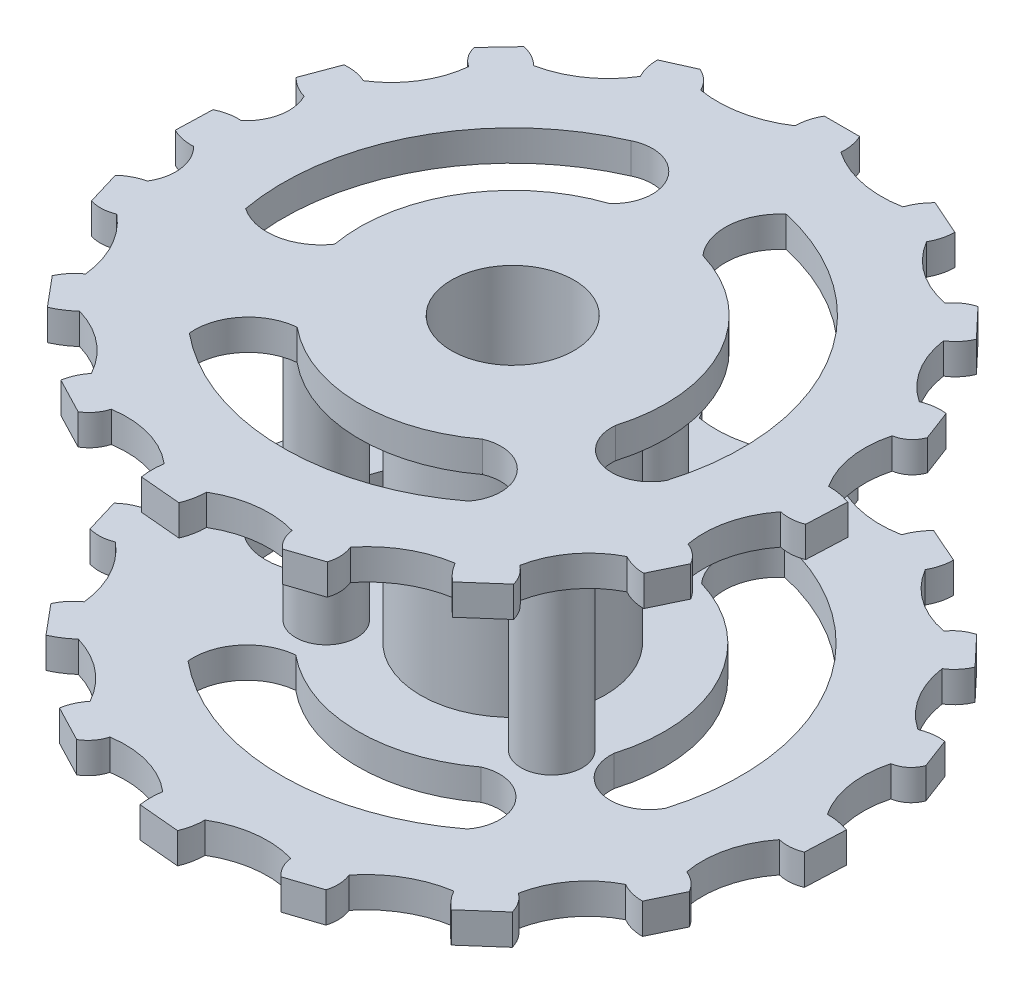
SolidWorks part; units mm, degrees
note: The reader was unsure of these and kept them because the rebuilt part matched: shared geometry of "Croquis5<6>".
ref_plane "Alzado" through (0, 0, 0) normal (0, 0, 1) x (1, 0, 0)
ref_plane "Planta" through (0, 0, 0) normal (0, 1, 0) x (1, 0, 0)
ref_plane "Vista lateral" through (0, 0, 0) normal (1, 0, 0) x (0, 0, -1)
sketch "Croquis1" plane through (0, 0, 0) normal (0, 1, 0) x (1, 0, 0)
  line L1 (7.418, 20.1666) -> (9.737, 19.1413)
  line L2 (14.6937, 15.6953) -> (16.489, 13.7972)
  line L3 (19.7018, 8.6076) -> (20.4553, 6.6204)
  line L4 (21.3822, -2.2476) -> (21.4965, 0.3858)
  line L5 (13.1137, -17.0376) -> (15.2348, -15.1707)
  line L6 (18.8688, -10.3062) -> (19.8608, -8.234)
  line L7 (5.6933, -20.7325) -> (7.8899, -20)
  line L8 (-2.9903, -21.2583) -> (-0.3023, -21.4979)
  line L9 (-8.7432, -19.6419) -> (-11.0959, -18.4155)
  line L10 (-15.6524, -14.7395) -> (-17.2801, -12.7925)
  line L11 (-20.2277, -7.2862) -> (-20.8986, -5.0496)
  line L12 (-21.4932, -0.5408) -> (-21.4205, 1.8468)
  line L13 (-20.53, 6.3852) -> (-19.6776, 8.6626)
  line L17 (1.2087, 21.4476) -> (-1.0939, 21.4476)
  line L24 (0, 8.75) -> (0, 7.75)
  line L27 (7.3634, -4.7268) -> (7.3634, -3.7268)
  line L28 (-7.3634, -4.7268) -> (-7.3634, -3.7268)
  line L33 (0, 20) -> (0, 19.3)
  line L34 (-9.7228, 19.176) -> (-7.8018, 20.0345)
  line L65 (-16.4043, 13.8978) -> (-14.8257, 15.5708)
  line L66 (-9.7228, 19.176) -> (-7.8018, 20.0345)
  arc A19 (-9.3513, 17.6792) -> (-9.7228, 19.176) centre (-6.5215, 19.176) cw
  arc A20 (-6.6037, 18.8783) -> (-7.8018, 20.0345) centre (-8.7432, 17.86) ccw
  arc A21 (19.8608, -2.3556) -> (21.3822, -2.2476) centre (20.4553, 0.0398) ccw
  arc A22 (19.9895, 0.6481) -> (21.4965, 0.3858) centre (19.9895, -3.8128) cw
  arc A23 (18.6573, -7.2045) -> (19.8608, -8.234) centre (17.7999, -9.4249) cw
  arc A24 (17.3725, -9.9095) -> (18.8688, -10.3062) centre (18.8688, -7.2862) ccw
  arc A25 (14.3713, -13.9092) -> (15.2348, -15.1707) centre (12.9424, -15.8135) cw
  arc A26 (12.1344, -15.8983) -> (13.1137, -17.0376) centre (15.6955, -13.8279) ccw
  arc A27 (7.8127, -18.4109) -> (7.8899, -20) centre (5.6933, -19.3103) cw
  arc A28 (4.9645, -19.374) -> (5.6933, -20.7325) centre (7.0961, -19.1053) ccw
  arc A29 (-2.9903, -19.7752) -> (-2.9903, -21.2583) centre (1.9139, -20.5168) ccw
  arc A30 (0, -20) -> (-0.3023, -21.4979) centre (-3.8625, -20) cw
  arc A31 (-7.8018, -18.4155) -> (-8.7432, -19.6419) centre (-9.8111, -17.8477) cw
  arc A32 (-10.4747, -17.0376) -> (-11.0959, -18.4155) centre (-8.1197, -18.9284) ccw
  arc A33 (-19.5247, -4.3341) -> (-20.8986, -5.0496) centre (-18.876, -7.2565) ccw
  arc A34 (-16.2897, -11.6037) -> (-17.2801, -12.7925) centre (-14.5249, -14.0811) ccw
  arc A35 (-14.3713, -13.9092) -> (-15.6524, -14.7395) centre (-17.6438, -10.2637) cw
  arc A36 (-18.6573, -7.2045) -> (-20.2277, -7.2862) centre (-19.5568, -5.0514) cw
  arc A37 (-19.8842, 2.1493) -> (-21.4205, 1.8468) centre (-20.0938, -0.8387) ccw
  arc A38 (-19.8492, -0.8562) -> (-21.4932, -0.5408) centre (-20.128, 2.1334) cw
  arc A39 (-19.2052, 5.582) -> (-20.53, 6.3852) centre (-18.3711, 8.4519) cw
  arc A40 (-18.1526, 8.3955) -> (-19.6776, 8.6626) centre (-19.4177, 5.6601) ccw
  arc A41 (-15.5056, 12.6323) -> (-16.4043, 13.8978) centre (-14.4368, 14.3432) cw
  arc A42 (-13.4419, 14.8093) -> (-14.8257, 15.5708) centre (-15.4964, 12.7141) ccw
  arc A43 (-1.5, 19.9437) -> (-1.0939, 21.4476) centre (1.488, 19.9437) cw
  arc A44 (1.488, 19.9437) -> (1.2087, 21.4476) centre (-1.5, 20.1666) ccw
  arc A45 (6.6037, 18.8783) -> (7.418, 20.1666) centre (9.7974, 17.7612) cw
  arc A47 (9.3513, 17.6792) -> (9.737, 19.1413) centre (6.773, 19.1413) ccw
  circle A48 centre (0, 0) radius 10
  arc A49 (1.488, 19.9437) -> (6.6037, 18.8783) centre (5.323, 25.5435) ccw
  arc A50 (9.3513, 17.6792) -> (13.4419, 14.8093) centre (14.5336, 20.7155) ccw
  arc A51 (15.5056, 12.6323) -> (18.1526, 8.3955) centre (21.6077, 13.4993) ccw
  arc A52 (19.2052, 5.582) -> (19.9895, 0.6481) centre (25.1101, 3.9913) ccw
  arc A53 (18.6573, -7.2045) -> (19.8608, -2.3556) centre (24.568, -6.0977) cw
  arc A54 (17.3725, -9.9095) -> (14.3713, -13.9092) centre (19.9576, -14.975) ccw
  arc A55 (12.1344, -15.8983) -> (7.8127, -18.4109) centre (13.1894, -22.686) ccw
  circle A56 centre (0, 0) radius 15
  arc A57 (0, -20) -> (4.9645, -19.374) centre (3.2011, -25.3884) cw
  arc A58 (-7.8018, -18.4155) -> (-2.9903, -19.7752) centre (-6.8649, -24.2932) cw
  arc A59 (-14.3713, -13.9092) -> (-10.4747, -17.0376) centre (-16.1823, -20.1557) cw
  arc A60 (-18.6573, -7.2045) -> (-16.2897, -11.6037) centre (-22.8771, -12.3123) cw
  arc A61 (-19.9895, -0.8568) -> (-19.5247, -4.3341) centre (-21.9152, -2.8839) cw
  arc A62 (-19.8842, 2.1493) -> (-19.2052, 5.582) centre (-21.712, 4.2943) ccw
  arc A63 (-18.1526, 8.3955) -> (-15.5056, 12.6323) centre (-21.1232, 13.1966) ccw
  arc A64 (-13.4419, 14.8093) -> (-9.3513, 17.6792) centre (-14.6867, 20.9337) ccw
  arc A65 (-6.6037, 18.8783) -> (-1.5, 19.9437) centre (-5.4022, 25.8803) ccw
  arc A66 (13.4419, 14.8093) -> (14.6937, 15.6953) centre (15.3083, 13.4999) cw
  arc A67 (15.5056, 12.6323) -> (16.489, 13.7972) centre (14.1868, 14.7433) ccw
  arc A68 (19.2052, 5.582) -> (20.4553, 6.6204) centre (18.9553, 7.1545) ccw
  arc A69 (18.1526, 8.3955) -> (19.7018, 8.6076) centre (19.3266, 5.5843) cw
  circle A71 centre (-7.3634, -4.7268) radius 1
  circle A72 centre (7.3634, -4.7268) radius 1
  circle A73 centre (0, 8.75) radius 1
  arc A74 (-6.0056, 13.7453) -> (-3.1657, 9.4857) centre (-4.878, 11.4206) cw
  arc A75 (3.2011, 14.6544) -> (2.8266, 9.5922) centre (5.545, 11.936) ccw
  arc A76 (14.3713, -4.2971) -> (9.5809, -2.8647) centre (12.1178, -3.1071) cw
  arc A77 (6.0162, -7.9878) -> (9.0619, -11.9534) centre (7.0185, -10.3703) cw
  arc A78 (-6.3717, -7.7072) -> (-9.5576, -11.5608) centre (-6.0378, -11.227) ccw
  arc A79 (-9.8388, -1.7882) -> (-14.7582, -2.6823) centre (-12.7456, 0.2245) cw
  circle A80 centre (0, 0) radius 1.5
  arc A81 (2.8266, 9.5922) -> (9.5809, -2.8647) centre (0, 0) cw
  arc A82 (6.0162, -7.9878) -> (-6.3717, -7.7072) centre (0, 0) cw
  arc A83 (-9.8388, -1.7882) -> (-3.1657, 9.4857) centre (0, 0) cw
  arc A84 (-6.0056, 13.7453) -> (-14.7582, -2.6823) centre (0, 0) ccw
  arc A85 (3.2011, 14.6544) -> (14.3713, -4.2971) centre (0, 0) cw
  arc A86 (9.0619, -11.9534) -> (-9.5576, -11.5608) centre (0, 0) cw
  dimension "D5" = 5
extrude "Saliente-Extruir1" add sketch "Croquis1" along normal blind 2
sketch "Croquis2" plane through (0, 2, 0) normal (0, 1, 0) x (1, 0, 0)
  line L0 (0, 0) -> (4, 0)
  line L1 (0, 0) -> (-6, 0)
  circle A2 centre (-7.3634, -4.7268) radius 2
  circle A3 centre (7.3634, -4.7268) radius 2
  circle A4 centre (0, 8.75) radius 2
  circle A5 centre (0, 0) radius 4
  dimension "D3" = 4
  dimension "D4" = 4
  dimension "D5" = 4
extrude "Saliente-Extruir2" add sketch "Croquis2" along normal blind 16.5
sketch "Croquis4" plane through (0, 18.5, 0) normal (0, 1, 0) x (1, 0, 0)
sketch "Croquis5" plane through (0, 18.5, 0) normal (0, 1, 0) x (1, 0, 0)
  line L0 (7.418, 20.2554) -> (9.737, 19.23)
  line L1 (14.6937, 15.7841) -> (16.489, 13.886)
  line L2 (19.7018, 8.6964) -> (20.4553, 6.7092)
  line L3 (21.3822, -2.1588) -> (21.4965, 0.4746)
  line L4 (13.1137, -16.9488) -> (15.2348, -15.0819)
  line L5 (18.8688, -10.2175) -> (19.8608, -8.1452)
  line L6 (5.6933, -20.6437) -> (7.8899, -19.9112)
  line L7 (-2.9903, -21.1695) -> (-0.3023, -21.4091)
  line L8 (-8.7432, -19.5531) -> (-11.0959, -18.3267)
  line L9 (-15.6524, -14.6507) -> (-17.2801, -12.7037)
  line L10 (-20.2277, -7.1974) -> (-20.8986, -4.9608)
  line L11 (-21.4932, -0.4521) -> (-21.4205, 1.9356)
  line L12 (-20.53, 6.4739) -> (-19.6776, 8.7514)
  line L13 (1.2087, 21.5364) -> (-1.0939, 21.5364)
  line L14 (0, 8.8388) -> (0, 7.8388)
  line L15 (7.3634, -4.638) -> (7.3634, -3.638)
  line L16 (-7.3634, -4.638) -> (-7.3634, -3.638)
  line L17 (0, 20.0888) -> (0, 19.3888)
  line L18 (-9.7228, 19.2648) -> (-7.8018, 20.1233)
  line L19 (-16.4043, 13.9866) -> (-14.8257, 15.6596)
  line L20 (-9.7228, 19.2648) -> (-7.8018, 20.1233)
  line L21 (0, 0.0888) -> (4, 0.0888)
  line L22 (0, 0.0888) -> (0, -5.9112)
  line L23 (0, 0) -> (3, 0)
  arc A0 (-9.3513, 17.768) -> (-9.7228, 19.2648) centre (-6.5215, 19.2648) cw
  arc A1 (-6.6037, 18.9671) -> (-7.8018, 20.1233) centre (-8.7432, 17.9488) ccw
  arc A2 (19.8608, -2.2668) -> (21.3822, -2.1588) centre (20.4553, 0.1285) ccw
  arc A3 (19.9895, 0.7369) -> (21.4965, 0.4746) centre (19.9895, -3.724) cw
  arc A4 (18.6573, -7.1157) -> (19.8608, -8.1452) centre (17.7999, -9.3361) cw
  arc A5 (17.3725, -9.8207) -> (18.8688, -10.2175) centre (18.8688, -7.1974) ccw
  arc A6 (14.3713, -13.8204) -> (15.2348, -15.0819) centre (12.9424, -15.7247) cw
  arc A7 (12.1344, -15.8095) -> (13.1137, -16.9488) centre (15.6955, -13.7392) ccw
  arc A8 (7.8127, -18.3221) -> (7.8899, -19.9112) centre (5.6933, -19.2215) cw
  arc A9 (4.9645, -19.2852) -> (5.6933, -20.6437) centre (7.0961, -19.0165) ccw
  arc A10 (-2.9903, -19.6864) -> (-2.9903, -21.1695) centre (1.9139, -20.428) ccw
  arc A11 (0, -19.9112) -> (-0.3023, -21.4091) centre (-3.8625, -19.9112) cw
  arc A12 (-7.8018, -18.3267) -> (-8.7432, -19.5531) centre (-9.8111, -17.7589) cw
  arc A13 (-10.4747, -16.9488) -> (-11.0959, -18.3267) centre (-8.1197, -18.8396) ccw
  arc A14 (-19.5247, -4.2453) -> (-20.8986, -4.9608) centre (-18.876, -7.1677) ccw
  arc A15 (-16.2897, -11.5149) -> (-17.2801, -12.7037) centre (-14.5249, -13.9923) ccw
  arc A16 (-14.3713, -13.8204) -> (-15.6524, -14.6507) centre (-17.6438, -10.1749) cw
  arc A17 (-18.6573, -7.1157) -> (-20.2277, -7.1974) centre (-19.5568, -4.9626) cw
  arc A18 (-19.8842, 2.2381) -> (-21.4205, 1.9356) centre (-20.0938, -0.7499) ccw
  arc A19 (-19.8492, -0.7674) -> (-21.4932, -0.4521) centre (-20.128, 2.2222) cw
  arc A20 (-19.2052, 5.6708) -> (-20.53, 6.4739) centre (-18.3711, 8.5407) cw
  arc A21 (-18.1526, 8.4843) -> (-19.6776, 8.7514) centre (-19.4177, 5.7489) ccw
  arc A22 (-15.5056, 12.7211) -> (-16.4043, 13.9866) centre (-14.4368, 14.432) cw
  arc A23 (-13.4419, 14.8981) -> (-14.8257, 15.6596) centre (-15.4964, 12.8028) ccw
  arc A24 (-1.5, 20.0325) -> (-1.0939, 21.5364) centre (1.488, 20.0325) cw
  arc A25 (1.488, 20.0325) -> (1.2087, 21.5364) centre (-1.5, 20.2554) ccw
  arc A26 (6.6037, 18.9671) -> (7.418, 20.2554) centre (9.7974, 17.8499) cw
  arc A27 (9.3513, 17.768) -> (9.737, 19.23) centre (6.773, 19.23) ccw
  circle A28 centre (0, 0.0888) radius 10
  arc A29 (1.488, 20.0325) -> (6.6037, 18.9671) centre (5.323, 25.6323) ccw
  arc A30 (9.3513, 17.768) -> (13.4419, 14.8981) centre (14.5336, 20.8043) ccw
  arc A31 (15.5056, 12.7211) -> (18.1526, 8.4843) centre (21.6077, 13.5881) ccw
  arc A32 (19.2052, 5.6708) -> (19.9895, 0.7369) centre (25.1101, 4.0801) ccw
  arc A33 (18.6573, -7.1157) -> (19.8608, -2.2668) centre (24.568, -6.0089) cw
  arc A34 (17.3725, -9.8207) -> (14.3713, -13.8204) centre (19.9576, -14.8862) ccw
  arc A35 (12.1344, -15.8095) -> (7.8127, -18.3221) centre (13.1894, -22.5972) ccw
  circle A36 centre (0, 0.0888) radius 15
  arc A37 (0, -19.9112) -> (4.9645, -19.2852) centre (3.2011, -25.2996) cw
  arc A38 (-7.8018, -18.3267) -> (-2.9903, -19.6864) centre (-6.8649, -24.2044) cw
  arc A39 (-14.3713, -13.8204) -> (-10.4747, -16.9488) centre (-16.1823, -20.067) cw
  arc A40 (-18.6573, -7.1157) -> (-16.2897, -11.5149) centre (-22.8771, -12.2235) cw
  arc A41 (-19.9895, -0.768) -> (-19.5247, -4.2453) centre (-21.9152, -2.7951) cw
  arc A42 (-19.8842, 2.2381) -> (-19.2052, 5.6708) centre (-21.712, 4.3831) ccw
  arc A43 (-18.1526, 8.4843) -> (-15.5056, 12.7211) centre (-21.1232, 13.2854) ccw
  arc A44 (-13.4419, 14.8981) -> (-9.3513, 17.768) centre (-14.6867, 21.0225) ccw
  arc A45 (-6.6037, 18.9671) -> (-1.5, 20.0325) centre (-5.4022, 25.9691) ccw
  arc A46 (13.4419, 14.8981) -> (14.6937, 15.7841) centre (15.3083, 13.5887) cw
  arc A47 (15.5056, 12.7211) -> (16.489, 13.886) centre (14.1868, 14.8321) ccw
  arc A48 (19.2052, 5.6708) -> (20.4553, 6.7092) centre (18.9553, 7.2433) ccw
  arc A49 (18.1526, 8.4843) -> (19.7018, 8.6964) centre (19.3266, 5.6731) cw
  circle A50 centre (-7.3634, -4.638) radius 1
  circle A51 centre (7.3634, -4.638) radius 1
  circle A52 centre (0, 8.8388) radius 1
  arc A53 (-6.0056, 13.8341) -> (-3.1657, 9.5745) centre (-4.878, 11.5094) cw
  arc A54 (3.2011, 14.7432) -> (2.8266, 9.681) centre (5.545, 12.0248) ccw
  arc A55 (14.3713, -4.2083) -> (9.5809, -2.7759) centre (12.1178, -3.0183) cw
  arc A56 (6.0162, -7.899) -> (9.0619, -11.8646) centre (7.0185, -10.2815) cw
  arc A57 (-6.3717, -7.6184) -> (-9.5576, -11.472) centre (-6.0378, -11.1382) ccw
  arc A58 (-9.8388, -1.6994) -> (-14.7582, -2.5935) centre (-12.7456, 0.3133) cw
  arc A60 (2.8266, 9.681) -> (9.5809, -2.7759) centre (0, 0.0888) cw
  arc A61 (6.0162, -7.899) -> (-6.3717, -7.6184) centre (0, 0.0888) cw
  arc A62 (-9.8388, -1.6994) -> (-3.1657, 9.5745) centre (0, 0.0888) cw
  arc A63 (-6.0056, 13.8341) -> (-14.7582, -2.5935) centre (0, 0.0888) ccw
  arc A64 (3.2011, 14.7432) -> (14.3713, -4.2083) centre (0, 0.0888) cw
  arc A65 (9.0619, -11.8646) -> (-9.5576, -11.472) centre (0, 0.0888) cw
  circle A66 centre (0, 0.0888) radius 4
  circle A67 centre (0, 0.0888) radius 4
  dimension "D1" = 5
extrude "Saliente-Extruir21" add sketch "Croquis5" along normal blind 2
sketch "Croquis6" plane through (0, 2, 0) normal (0, 1, 0) x (1, 0, 0)
extrude "Saliente-Extruir28" add sketch "Croquis5<6>" along normal blind 2
sketch "Croquis5<6>" plane through (0, 18.5, 0) normal (0, 1, 0) x (1, 0, 0) same geometry as "Croquis5"
sketch "Croquis7" plane through (0, 18.5, 0) normal (0, -1, 0) x (1, 0, 0)
  line L0 (0, -0.0888) -> (6, -0.0888)
  circle A0 centre (0, -0.0888) radius 4
  circle A1 centre (0, -0.0888) radius 6
extrude "Saliente-Extruir29" add sketch "Croquis7" along normal blind 16.5
sketch "Croquis8" plane through (0, 20.5, 0) normal (0, 1, 0) x (1, 0, 0)
  line L0 (0, 0) -> (3, 0)
  circle A0 centre (0, 0) radius 4.0888
  circle A1 centre (0, 0) radius 3
sketch "Croquis10" plane through (0, 0, 0) normal (0, -1, 0) x (1, 0, 0)
  point P0 (0, 0)
sketch "Croquis11" plane through (0, 20.5, 0) normal (0, 1, 0) x (1, 0, 0)
  point P0 (0, 0)
